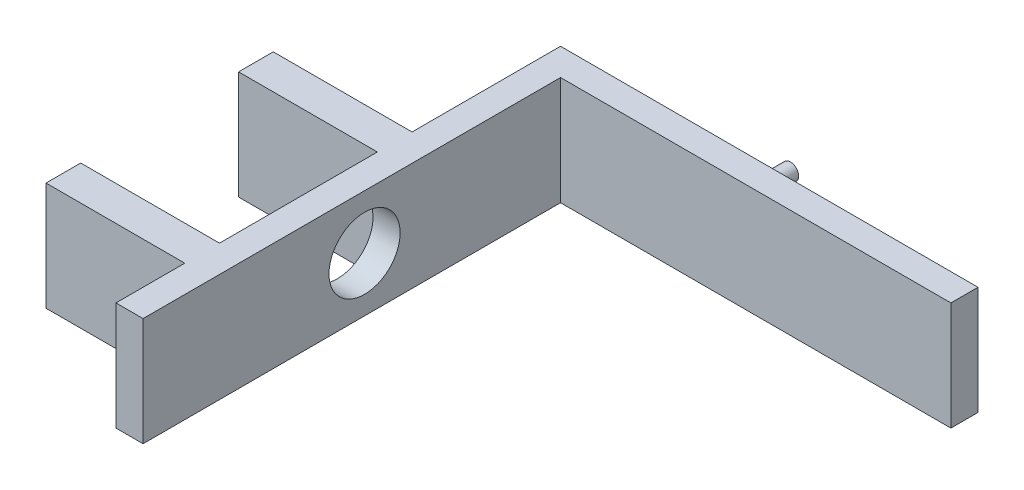
SolidWorks part; units mm, degrees
ref_plane "Front Plane" through (0, 0, 0) normal (0, 0, 1) x (1, 0, 0)
ref_plane "Top Plane" through (0, 0, 0) normal (0, 1, 0) x (1, 0, 0)
ref_plane "Right Plane" through (0, 0, 0) normal (1, 0, 0) x (0, 0, -1)
sketch "Sketch1" plane through (0, 0, 0) normal (0, 1, 0) x (1, 0, 0)
  line L1 (-2.7577, -19.8611) -> (1.211, -19.8611)
  line L2 (-2.7577, -19.8611) -> (-2.7577, 45.2264)
  line L3 (-2.7577, 45.2264) -> (6.2797, 45.2264)
  line L4 (1.211, -19.8611) -> (1.211, 41.2577)
  line L5 (-2.7577, -19.8611) -> (6.2797, 45.2264) construction
  line L6 (-2.7577, 45.2264) -> (1.211, -19.8611) construction
  line L7 (6.2797, 45.2264) -> (58.361, 45.2264)
  line L9 (1.211, 41.2577) -> (58.361, 41.2577)
  line L10 (58.361, 45.2264) -> (58.361, 41.2577)
  point P0 (0, 0)
  dimension "D1" = 3.9688
  dimension "D2" = 3.9688
  dimension "D3" = 57.15
  dimension "D4" = 61.1187
extrude "Boss-Extrude1" add sketch "Sketch1" along normal mid plane 15.875
sketch "Sketch3" plane through (-2.7577, 0, 0) normal (-1, 0, 0) x (0, 0, 1)
  circle A0 centre (-12.5666, 0) radius 5.207
  dimension "D1" = 10.414
extrude "Cut-Extrude1" cut sketch "Sketch3" against normal up to surface (3.9688 mm away) up to face at (1.211, 0, -10.6983)
sketch "Sketch4" plane through (0, 0, -45.2264) normal (0, 0, -1) x (-1, 0, 0)
  line L0 (-58.361, 7.9375) -> (-58.361, -7.9375) construction
  circle A0 centre (-22.0073, 0) radius 1.2065
  dimension "D1" = 2.413
  dimension "D2" = 36.3537
extrude "Boss-Extrude2" add sketch "Sketch4" along normal blind 8.89
sketch "Sketch5" plane through (-2.7577, 0, 0) normal (-1, 0, 0) x (0, 0, 1)
  line L0 (-45.2264, 7.9375) -> (19.8611, 7.9375) construction
  line L1 (-23.4886, -7.9375) -> (-18.4086, -7.9375)
  line L2 (-23.4886, -7.9375) -> (-23.4886, 7.9375)
  line L3 (-23.4886, 7.9375) -> (-18.4086, 7.9375)
  line L4 (-18.4086, -7.9375) -> (-18.4086, 7.9375)
  line L5 (-23.4886, -7.9375) -> (-18.4086, 7.9375) construction
  line L6 (-23.4886, 7.9375) -> (-18.4086, -7.9375) construction
  line L7 (-45.2264, -7.9375) -> (19.8611, -7.9375) construction
  line L9 (9.7854, 7.9375) -> (4.7054, 7.9375)
  line L10 (9.7854, 7.9375) -> (9.7854, -7.9375)
  line L11 (9.7854, -7.9375) -> (4.7054, -7.9375)
  line L12 (4.7054, 7.9375) -> (4.7054, -7.9375)
  circle A1 centre (-12.5666, 0) radius 5.207 construction
  point P0 (-20.9486, 0)
  dimension "D3" = 17.272
  dimension "D1" = 5.842
  dimension "D2" = 5.08
  dimension "D4" = 5.08
extrude "Boss-Extrude3" add sketch "Sketch5" along normal blind 20.32
